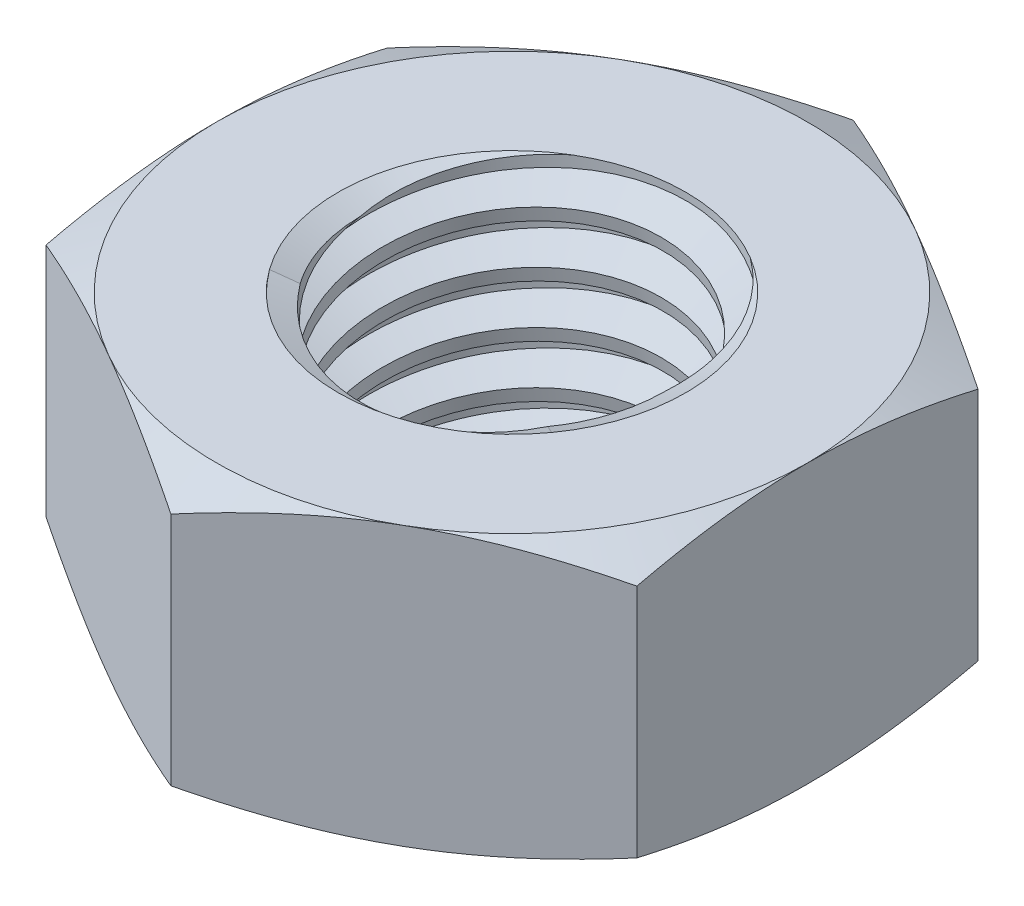
SolidWorks part; units mm, degrees
ref_plane "Front" through (0, 0, 0) normal (0, 0, 1) x (1, 0, 0)
ref_plane "Top" through (0, 0, 0) normal (0, 1, 0) x (1, 0, 0)
ref_plane "Right" through (0, 0, 0) normal (1, 0, 0) x (0, 0, -1)
sketch "Sketch1" plane through (0, 0, 0) normal (0, 1, 0) x (1, 0, 0)
  line L1 (0, 9.815) -> (-8.5, 4.9075)
  line L2 (-8.5, 4.9075) -> (-8.5, -4.9075)
  line L3 (-8.5, -4.9075) -> (0, -9.815)
  line L4 (0, -9.815) -> (8.5, -4.9075)
  line L5 (8.5, -4.9075) -> (8.5, 4.9075)
  line L6 (8.5, 4.9075) -> (0, 9.815)
  circle A0 centre (0, 0) radius 8.5 construction
  dimension "Hex Flats" = 17
extrude "Extrude1" add sketch "Sketch1" along normal mid plane 8
sketch "Sketch2" plane through (0, 0, 0) normal (1, 0, 0) x (0, 0, -1)
  line L0 (-5, -4) -> (-5, 4) construction
  line L1 (0, -4) -> (5, -4)
  line L2 (0, -4) -> (0, 4)
  line L3 (0, 4) -> (5, 4)
  line L4 (5, -4) -> (5, 4)
  line L5 (-4.9075, 4) -> (4.9075, 4) construction
  line L6 (-4.9075, -4) -> (4.9075, -4) construction
  line L7 (0, -9) -> (0, -4) construction
  dimension "Thread Dia" = 10
revolve "Revolve1" add sketch "Sketch2" angle 360 about L7
sketch "Sketch3" plane through (0, 0, 0) normal (1, 0, 0) x (0, 0, -1)
  line L0 (5, 4) -> (-5, 4) construction
  line L1 (-5, 4) -> (-5, 2.5) construction
  line L2 (-5, 2.5) -> (5, 4) construction
  line L3 (5, 4) -> (5.0278, 3.8146) construction
  line L4 (5.0278, 3.8146) -> (5.2225, 2.5166)
  line L5 (5.2225, 2.5166) -> (4.3501, 2.8597)
  line L6 (4.3501, 2.8597) -> (4.2944, 3.2306)
  line L7 (4.2944, 3.2306) -> (5.0278, 3.8146)
  line L8 (4.3222, 3.0451) -> (5.1252, 3.1656) construction
  line L9 (5, 4) -> (5, 3.1468) construction
  line L10 (5, 3.1468) -> (-5, 1.6468) construction
  line L11 (-5, 1.6468) -> (-5, 2.5) construction
  line L12 (-0.2405, 4) -> (0.2405, 0.7936) construction
  line L13 (-5, -4) -> (-5, 4) construction
  line L14 (0, 4) -> (5, 4) construction
  line L15 (5, -4) -> (5, 4) construction
  line L16 (0, 0) -> (0, 4) construction
  line L17 (-5.0278, 3.8146) -> (-5.2225, 2.5166) construction
  line L18 (-4.2944, 3.2306) -> (-5.0278, 3.8146) construction
  line L19 (-4.3501, 2.8597) -> (-4.2944, 3.2306) construction
  line L20 (-5.2225, 2.5166) -> (-4.3501, 2.8597) construction
  line L21 (0.2405, 4) -> (-0.2405, 0.7936) construction
  point P13 (0, 2.3968)
  dimension "D1" = 0.1875
  dimension "D2" = 0.375
  dimension "Thread Pitch" = 1.5
  dimension "D4" = 60
  dimension "D5" = 1.5
revolve "Cut-Revolve1" cut sketch "Sketch3" angle 360 about L12
pattern_linear "LPattern1" count 5 spacing 1.5 along (0, -1, 0) count 2 spacing 1.5 along (0, 1, 0) of "Cut-Revolve1"
sketch "Sketch4" plane through (0, 0, 0) normal (1, 0, 0) x (0, 0, -1)
  line L0 (0, 4) -> (5, 4)
  line L1 (5, 4) -> (4.2944, 3.671)
  line L2 (4.2944, 3.671) -> (4.2944, -3.671)
  line L3 (4.2944, -3.671) -> (5, -4)
  line L4 (5, -4) -> (0, -4)
  line L5 (0, -4) -> (0, 4)
  line L6 (5, -4) -> (5, 4) construction
  line L7 (0, 4) -> (5, 4) construction
  line L8 (0, -4) -> (5, -4) construction
  line L9 (0, -4) -> (0, 4) construction
  line L10 (0, 4) -> (0, 4.7785) construction
  dimension "D1" = 25
revolve "Cut-Revolve2" cut sketch "Sketch4" angle 360 about L10
combine bodies "Combine1" operation type subtract main body 112 bodies to subtract 111
sketch "Sketch5" plane through (0, 0, 0) normal (1, 0, 0) x (0, 0, -1)
  line L0 (0, -4) -> (8.5, -4)
  line L1 (8.5, -4) -> (9.815, -3.3868)
  line L2 (9.815, -3.3868) -> (9.815, 3.3868)
  line L3 (9.815, 3.3868) -> (8.5, 4)
  line L4 (0, 4) -> (0, 5.27)
  line L5 (0, 5.27) -> (11.085, 5.27)
  line L6 (11.085, 5.27) -> (11.085, -5.27)
  line L7 (11.085, -5.27) -> (0, -5.27)
  line L8 (0, -5.27) -> (0, -4)
  line L9 (8.5, 4) -> (8.5, -4) construction
  line L11 (0, -4) -> (5, -4) construction
  line L12 (8.5, 4) -> (0, 4)
  line L13 (9.815, 0) -> (11.085, 0) construction
  line L14 (9.815, 4) -> (9.815, -4) construction
  line L15 (0, -4) -> (0, 4) construction
  line L17 (0, 0) -> (8.5, 0) construction
  line L22 (0, 4) -> (5, 4) construction
  dimension "D1" = 25
  dimension "D2" = 1.27
  dimension "D3" = 8
revolve "Cut-Revolve3" cut sketch "Sketch5" angle 360 about L15
equation "\"D1@Sketch3\"=\"Thread Pitch@Sketch3\"/8"
equation "\"D2@Sketch3\"=\"Thread Pitch@Sketch3\"/4"
equation "\"D5@Sketch3\"=\"Thread Pitch@Sketch3\""
equation "\"D4@LPattern1\"=\"Thread Pitch@Sketch3\""
equation "\"D3@LPattern1\"=\"Thread Pitch@Sketch3\""
equation "\"D1@LPattern1\"=\"Height@Extrude1\"/\"Thread Pitch@Sketch3\""
